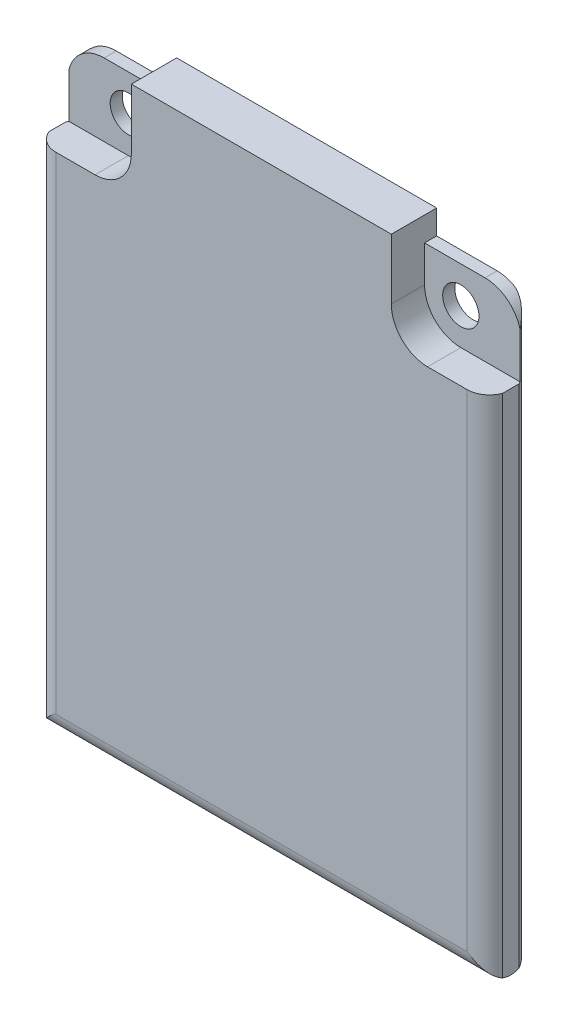
SolidWorks part; units mm, degrees
ref_plane "Plano frontal" through (0, 0, 0) normal (0, 0, 1) x (1, 0, 0)
ref_plane "Plano superior" through (0, 0, 0) normal (0, 1, 0) x (1, 0, 0)
ref_plane "Plano direito" through (0, 0, 0) normal (1, 0, 0) x (0, 0, -1)
sketch "Esboço1" plane through (0, 0, 0) normal (0, 0, 1) x (1, 0, 0)
  line L0 (-10.75, 25) -> (10.75, 25)
  line L1 (-18.75, 25) -> (18.75, 25) construction
  line L2 (-18.75, 25) -> (-18.75, -25) construction
  line L3 (-18.75, -25) -> (18.75, -25) construction
  line L4 (18.75, 25) -> (18.75, -25) construction
  line L5 (-18.75, 25) -> (18.75, -25) construction
  line L6 (-18.75, -25) -> (18.75, 25) construction
  line L7 (10.75, 25) -> (10.75, 20)
  line L8 (-10.75, 25) -> (-10.75, 20)
  line L9 (13.75, 17) -> (18.75, 17)
  line L10 (-13.75, 17) -> (-18.75, 17)
  line L11 (-18.75, 17) -> (-18.75, -25)
  line L12 (-18.75, -25) -> (18.75, -25)
  line L13 (18.75, -25) -> (18.75, 17)
  line L14 (-18.75, 23) -> (18.75, 23) construction
  line L15 (-10.75, 23) -> (-15.75, 23)
  line L16 (-18.75, 20) -> (-18.75, 17)
  line L17 (10.75, 23) -> (15.75, 23)
  line L18 (18.75, 20) -> (18.75, 17)
  arc A0 (10.75, 20) -> (13.75, 17) centre (13.75, 20) ccw
  arc A1 (-10.75, 20) -> (-13.75, 17) centre (-13.75, 20) cw
  circle A2 centre (-13.75, 20) radius 1.5
  circle A3 centre (13.75, 20) radius 1.5
  arc A4 (-15.75, 23) -> (-18.75, 20) centre (-15.75, 20) ccw
  arc A5 (15.75, 23) -> (18.75, 20) centre (15.75, 20) cw
  point P0 (0, 0)
  point P14 (10.75, 17)
  point P17 (-10.75, 17)
  dimension "D7" = 3
  dimension "D8" = 3
  dimension "D9" = 3
  dimension "D11" = 3
  dimension "D1" = 37.5
  dimension "D2" = 50
  dimension "D3" = 8
  dimension "D4" = 8
  dimension "D5" = 8
  dimension "D6" = 8
  dimension "D10" = 2
extrude "Ressalto-extrusão1" add sketch "Esboço1" along normal blind 3.75 contours L8 A1 L10 L11 L12 L13 L9 A0 L7 L0 region at (0, -1.4963, 0)
extrude "Ressalto-extrusão2" add sketch "Esboço1<3>" along normal blind 1 contours A5 L17 L7 A0 L9 L18 A3 | L15 A4 L16 L10 A1 L8 A2 region at (-10.85, 21.5, 0) region at (13.25, 22.9, 0)
sketch "Esboço1<3>" plane through (0, 0, 0) normal (0, 0, 1) x (1, 0, 0) same geometry as "Esboço1"
sketch "Esboço3" plane through (-18.75, 0, 0) normal (-1, 0, 0) x (0, 0, 1)
  line L0 (3.75, -22.983) -> (0, -22.983) construction
  line L6 (0, 20) -> (0, -25)
  line L7 (0, -25) -> (3.75, -25)
  line L8 (3.75, -25) -> (3.75, 17)
  line L9 (3.75, 17) -> (1, 17)
  line L10 (1, 17) -> (1, 20)
  line L11 (1, 20) -> (0, 20)
  line L12 (0, 20) -> (0, -25) construction
  line L13 (0, -25) -> (3.75, -25)
  line L14 (3.75, -25) -> (3.75, 17) construction
  line L15 (3.75, 17) -> (1, 17) construction
  line L16 (1, 17) -> (1, 20) construction
  line L17 (1, 20) -> (0, 20) construction
  arc A0 (3.75, -22.983) -> (0, -22.983) centre (1.875, -23.12) cw
  line M7 (0, 20) -> (0, -25)
  line M8 (0, -25) -> (3.75, -25)
  line M9 (3.75, -25) -> (3.75, 17)
  dimension "D2" = 1.88
  dimension "D1" = 0
extrude "Corte-extrusão1" cut sketch "Esboço3" against normal through all contours A0 L13 M9 | A0 M8 M7 region at (-18.75, -24.5857, 0.4199) region at (-18.75, -24.5857, 3.3301)
sketch "Esboço4" plane through (0, 25, 0) normal (0, 1, 0) x (1, 0, 0)
  line L0 (0, 0) -> (0, -3.75) construction
  line L1 (-10.75, 0) -> (10.75, 0) construction
  line L2 (-10.75, -3.75) -> (10.75, -3.75) construction
  line L3 (17, -1.875) -> (-17, -1.875) construction
  line L4 (17, -3.75) -> (-17, -3.75)
  line L5 (17, 0) -> (-17, 0)
  line L6 (17, -4.75) -> (-17, -4.75)
  line L7 (17, 1) -> (-17, 1)
  arc A0 (17, -3.75) -> (17, 0) centre (17, -1.875) ccw
  arc A1 (-17, 0) -> (-17, -3.75) centre (-17, -1.875) ccw
  arc A2 (-17, 1) -> (-17, -4.75) centre (-17, -1.875) ccw
  arc A3 (17, -4.75) -> (17, 1) centre (17, -1.875) ccw
  point P8 (0, -1.875)
  dimension "D1" = 34
  dimension "D2" = 1
extrude "Corte-extrusão2" cut sketch "Esboço4" against normal through all
